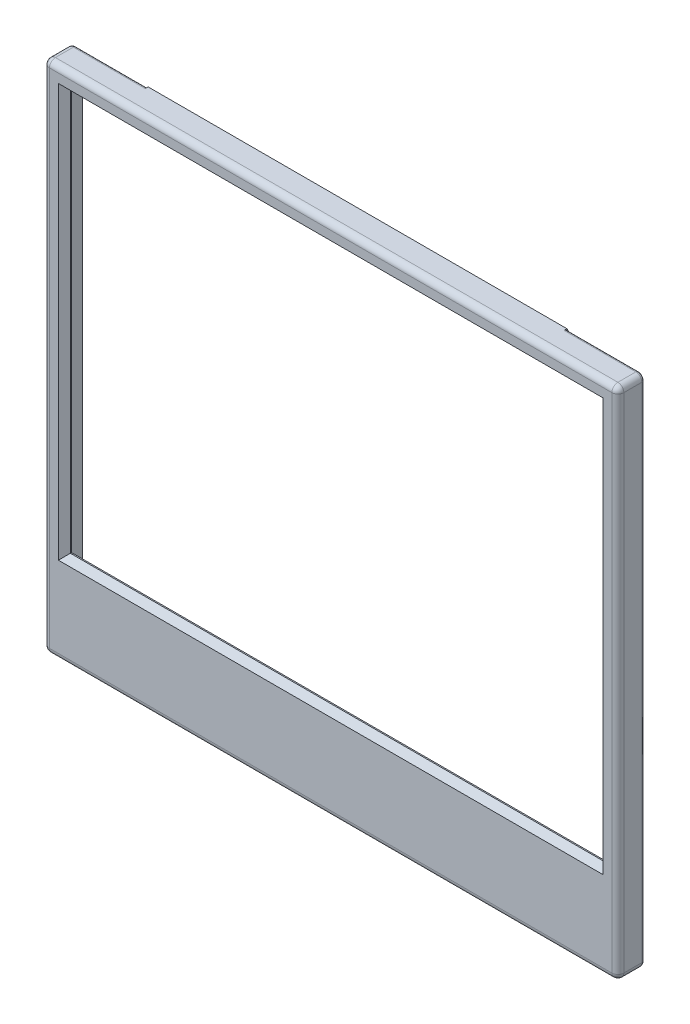
SolidWorks part; units mm, degrees
ref_plane "Front Plane" through (0, 0, 0) normal (0, 0, 1) x (1, 0, 0)
ref_plane "Top Plane" through (0, 0, 0) normal (0, 1, 0) x (1, 0, 0)
ref_plane "Right Plane" through (0, 0, 0) normal (1, 0, 0) x (0, 0, -1)
sketch "Sketch1" plane through (0, 0, 0) normal (0, 0, 1) x (1, 0, 0)
  line L0 (44.5, 68.5) -> (44.5, 67) construction
  line L1 (0, 0) -> (89, 0)
  line L2 (0, 0) -> (0, 67)
  line L3 (0, 67) -> (89, 67)
  line L4 (89, 0) -> (89, 67)
  line L5 (90.5, 68.5) -> (-1.5, 68.5) construction
  line L6 (90.5, 68.5) -> (90.5, -8.5) construction
  line L7 (90.5, -8.5) -> (-1.5, -8.5) construction
  line L8 (-1.5, 68.5) -> (-1.5, -8.5) construction
  line L9 (0, 33.5) -> (-1.5, 33.5) construction
  line L10 (44.5, 68.5) -> (44.5, 70.5) construction
  line L11 (-3.5, 70.5) -> (92.5, 70.5)
  line L12 (-3.5, 70.5) -> (-3.5, -15.5)
  line L13 (-3.5, -15.5) -> (92.5, -15.5)
  line L14 (92.5, 70.5) -> (92.5, -15.5)
  line L15 (-1.5, 68.5) -> (-1.5, 70.5) construction
  line L16 (-1.5, 68.5) -> (-3.5, 68.5) construction
  dimension "D1" = 89
  dimension "D2" = 67
  dimension "D3" = 92
  dimension "D4" = 77
  dimension "D5" = 2
  dimension "D6" = 7
extrude "Boss-Extrude1" add sketch "Sketch1" along normal blind 4.5
sketch "Sketch2" plane through (0, 0, 0) normal (0, 0, -1) x (-1, 0, 0)
  line L0 (-44.5, 68.5) -> (-44.5, 70.5) construction
  line L1 (-90.5, -9.5) -> (1.5, -9.5)
  line L2 (-90.5, -9.5) -> (-90.5, 68.5)
  line L3 (-90.5, 68.5) -> (1.5, 68.5)
  line L4 (1.5, -9.5) -> (1.5, 68.5)
  line L5 (-92.5, 70.5) -> (3.5, 70.5) construction
  line L6 (-90.5, 68.5) -> (-90.5, 70.5) construction
  line L7 (-90.5, 68.5) -> (-92.5, 68.5) construction
  line L8 (-92.5, -15.5) -> (-92.5, 70.5) construction
  dimension "D1" = 92
  dimension "D2" = 78
extrude "Cut-Extrude1" cut sketch "Sketch2" against normal blind 3.3
chamfer "Chamfer1" distance 1 angle 45 4 edges at (89, 33.5, 4.5) (44.5, 67, 4.5) (44.5, 0, 4.5) (0, 33.5, 4.5)
sketch "Sketch3" plane through (0, 0, 0) normal (0, 0, -1) x (-1, 0, 0)
  line L0 (3.5, -15.5) -> (-92.5, -15.5) construction
  line L1 (-7.1, -15.5) -> (-21.9, -15.5)
  line L2 (-7.1, -15.5) -> (-7.1, -9.5)
  line L3 (-7.1, -9.5) -> (-21.9, -9.5)
  line L4 (-81.9, -15.5) -> (-81.9, -9.5)
  line L5 (-90.5, -9.5) -> (1.5, -9.5) construction
  line L7 (-44.5, -15.5) -> (-44.5, -9.5) construction
  line L8 (-67.1, -9.5) -> (-81.9, -9.5)
  line L10 (-67.1, -9.5) -> (-67.1, -15.5)
  line L12 (-51.9, -9.5) -> (-51.9, -15.5)
  line L14 (-37.1, -9.5) -> (-37.1, -15.5)
  line L16 (-21.9, -9.5) -> (-21.9, -15.5)
  line L17 (-67.1, -15.5) -> (-81.9, -15.5)
  line L18 (-37.1, -9.5) -> (-51.9, -9.5)
  line L19 (-37.1, -15.5) -> (-51.9, -15.5)
  line L20 (-67.1, -12.5) -> (-51.9, -12.5) construction
  line L21 (-37.1, -12.5) -> (-21.9, -12.5) construction
  line L22 (-59.5, -12.5) -> (-59.5, -20.7776) construction
  line L24 (-59.5, -20.7776) -> (-29.5, -20.7776) construction
  line L25 (-29.5, -20.7776) -> (-29.5, -12.5) construction
  point P8 (-44.5, -15.5)
  point P25 (-44.5, -15.5)
  point P27 (-44.5, -20.7776)
  point P29 (-28.789, -22.89)
  point P30 (-59.7142, -21.2679)
  point P31 (-82, -15.5)
  dimension "D1" = 15.2
  dimension "D2" = 30
extrude "Boss-Extrude2" add sketch "Sketch3" along normal blind 6
sketch "Sketch4" plane through (7.1, 0, 0) normal (-1, 0, 0) x (0, 0, 1)
  line L0 (-6, -9.5) -> (0, -9.5) construction
  line L1 (-6, -15.5) -> (0, -15.5) construction
  line L2 (-6, -15.5) -> (-6, -9.5) construction
  line L3 (-3, -9.5) -> (-6, -9.5)
  line L4 (-6, -9.5) -> (-6, -15.5)
  line L5 (-6, -15.5) -> (-3, -15.5)
  arc A0 (-3, -9.5) -> (-3, -15.5) centre (-3, -12.5) ccw
  circle A1 centre (-3, -12.5) radius 1.5
  line M3 (0, -9.5) -> (-6, -9.5)
  line M4 (-6, -9.5) -> (-6, -15.5)
  line M5 (-6, -15.5) -> (0, -15.5)
  dimension "D1" = 3
extrude "Cut-Extrude2" cut sketch "Sketch4" against normal through all contours A0 M3 M4 | A0 L4 M5 | A1
fillet "Fillet1" radius 1 8 edges at (92.5, 27.5, 4.5) (44.5, -15.5, 4.5) (-3.5, 27.5, 4.5) (44.5, 70.5, 4.5) (92.5, 70.5, 2.25) (92.5, -15.5, 2.25) (-3.5, -15.5, 2.25) (-3.5, 70.5, 2.25)
sketch "Sketch6" plane through (0, 0, 0) normal (0, 0, -1) x (-1, 0, 0)
  line L0 (-91.5, 70.5) -> (2.5, 70.5) construction
  line L1 (-79.5, 70.5) -> (-69.5, 70.5)
  line L2 (-79.5, 70.5) -> (-79.5, 66.3)
  line L3 (-79.5, 66.3) -> (-69.5, 66.3)
  line L4 (-9.5, 70.5) -> (-9.5, 66.3)
  line L5 (-44.5, 68.5) -> (-44.5, 66.3) construction
  line L6 (1.5, 68.5) -> (-90.5, 68.5) construction
  line L7 (-49.5, 70.5) -> (-39.5, 70.5)
  line L9 (-69.5, 66.3) -> (-69.5, 70.5)
  line L11 (-49.5, 66.3) -> (-49.5, 70.5)
  line L13 (-39.5, 66.3) -> (-39.5, 70.5)
  line L15 (-19.5, 66.3) -> (-19.5, 70.5)
  line L16 (-49.5, 66.3) -> (-39.5, 66.3)
  line L17 (-19.5, 70.5) -> (-9.5, 70.5)
  line L18 (-19.5, 66.3) -> (-9.5, 66.3)
  line L19 (-69.5, 68.4) -> (-49.5, 68.4) construction
  line L20 (-39.5, 68.4) -> (-19.5, 68.4) construction
  point P18 (-44.5, 66.3)
  dimension "D1" = 10
  dimension "D2" = 20
  dimension "D3" = 2.2
extrude "Boss-Extrude3" add sketch "Sketch6" along normal blind 1
chamfer "Chamfer2" distance 1 angle 63 3 edges at (14.5, 70.5, -1) (44.5, 70.5, -1) (74.5, 70.5, -1)
chamfer "Chamfer3" distance 0.5 angle 40 3 edges at (14.5, 66.3, 0) (44.5, 66.3, 0) (74.5, 66.3, 0)
fillet "Fillet2" radius 0.5 40 edges at (3.5, 70.5, 0) (85.5, 70.5, 0) (-3.2071, 70.2071, 0) (92.2071, 70.2071, 0) (-3.5, 27.5, 0) (92.5, 27.5, 0) (-3.2071, -15.2071, 0) (92.2071, -15.2071, 0) (2.8, -9.5, 0) (2.3, -15.5, 0) (29.5, -9.5, 0) (29.5, -15.5, 0) (59.5, -9.5, 0) (59.5, -15.5, 0) (86.2, -9.5, 0) (86.7, -15.5, 0) (7.1, -9.5, -1.5) (7.1, -15.5, -1.5) (21.9, -9.5, -1.5) (21.9, -15.5, -1.5) (37.1, -15.5, -1.5) (37.1, -9.5, -1.5) (51.9, -9.5, -1.5) (51.9, -15.5, -1.5) (67.1, -15.5, -1.5) (67.1, -9.5, -1.5) (81.9, -9.5, -1.5) (81.9, -15.5, -1.5) (7.1, -12.5, -6) (21.9, -12.5, -6) (7.1, -12.5, 0) (81.9, -12.5, 0) (51.9, -12.5, 0) (21.9, -12.5, 0) (37.1, -12.5, -6) (51.9, -12.5, -6) (67.1, -12.5, -6) (81.9, -12.5, -6) (37.1, -12.5, 0) (67.1, -12.5, 0)
fillet "Fillet3" radius 0.5 27 edges at (14.5, 66.3, -1) (19.5, 67.4187, -1) (14.5, 68.5374, -1) (9.5, 67.4187, -1) (44.5, 66.3, -1) (49.5, 67.4187, -1) (44.5, 68.5374, -1) (39.5, 67.4187, -1) (74.5, 66.3, -1) (79.5, 67.4187, -1) (74.5, 68.5374, -1) (69.5, 67.4187, -1) (74.5, 66.3, -0.4195) (69.5, 66.55, -0.2098) (74.5, 66.8, 0) (79.5, 66.55, -0.2098) (14.5, 66.3, -0.4195) (9.5, 66.55, -0.2098) (14.5, 66.8, 0) (19.5, 66.55, -0.2098) (44.5, 66.3, -0.4195) (39.5, 66.55, -0.2098) (44.5, 66.8, 0) (49.5, 66.55, -0.2098) (14.5, 68.5, 0) (44.5, 68.5, 0) (74.5, 68.5, 0)
sketch "Sketch7" plane through (0, -9.5, 0) normal (0, 1, 0) x (1, 0, 0)
  line L0 (44.5, -3.3) -> (44.5, 0) construction
  line L1 (90.5, -3.3) -> (-1.5, -3.3) construction
  line L2 (74.5, 3) -> (74.5, 1.5) construction
  line L3 (40.5, 0) -> (48.5, 0)
  line L4 (40.5, 0) -> (40.5, 1.5)
  line L5 (40.5, 1.5) -> (48.5, 1.5)
  line L6 (48.5, 0) -> (48.5, 1.5)
  line L7 (78.5, 0) -> (70.5, 0)
  line L8 (78.5, 0) -> (78.5, 1.5)
  line L9 (78.5, 1.5) -> (70.5, 1.5)
  line L10 (70.5, 0) -> (70.5, 1.5)
  line L11 (18.5, 0) -> (10.5, 0)
  line L12 (18.5, 0) -> (18.5, 1.5)
  line L13 (18.5, 1.5) -> (10.5, 1.5)
  line L14 (10.5, 0) -> (10.5, 1.5)
  line L15 (81.4, 3) -> (67.6, 3) construction
  line L16 (14.5, 3) -> (14.5, 1.5) construction
  line L17 (21.4, 3) -> (7.6, 3) construction
  point P8 (44.5, 0)
  dimension "D1" = 3.3
  dimension "D2" = 1.5
  dimension "D3" = 8
extrude "Boss-Extrude4" add sketch "Sketch7" along normal blind 1.25
chamfer "Chamfer4" distance 0.5 angle 40 3 edges at (14.5, -8.25, 0) (44.5, -8.25, 0) (74.5, -8.25, 0)
fillet "Fillet6" radius 0.5 27 edges at (18.5, -9.5, -0.75) (10.5, -9.5, -0.75) (48.5, -9.5, -0.75) (40.5, -9.5, -0.75) (78.5, -9.5, -0.75) (70.5, -9.5, -0.75) (18.5, -8.25, -0.9598) (14.5, -8.25, -0.4195) (10.5, -8.25, -0.9598) (78.5, -8.25, -0.9598) (74.5, -8.25, -0.4195) (70.5, -8.25, -0.9598) (48.5, -8.25, -0.9598) (44.5, -8.25, -0.4195) (40.5, -8.25, -0.9598) (18.5, -8.875, -1.5) (14.5, -8.25, -1.5) (10.5, -8.875, -1.5) (14.5, -9.5, -1.5) (48.5, -8.875, -1.5) (44.5, -8.25, -1.5) (40.5, -8.875, -1.5) (44.5, -9.5, -1.5) (78.5, -8.875, -1.5) (74.5, -8.25, -1.5) (70.5, -8.875, -1.5) (74.5, -9.5, -1.5)
